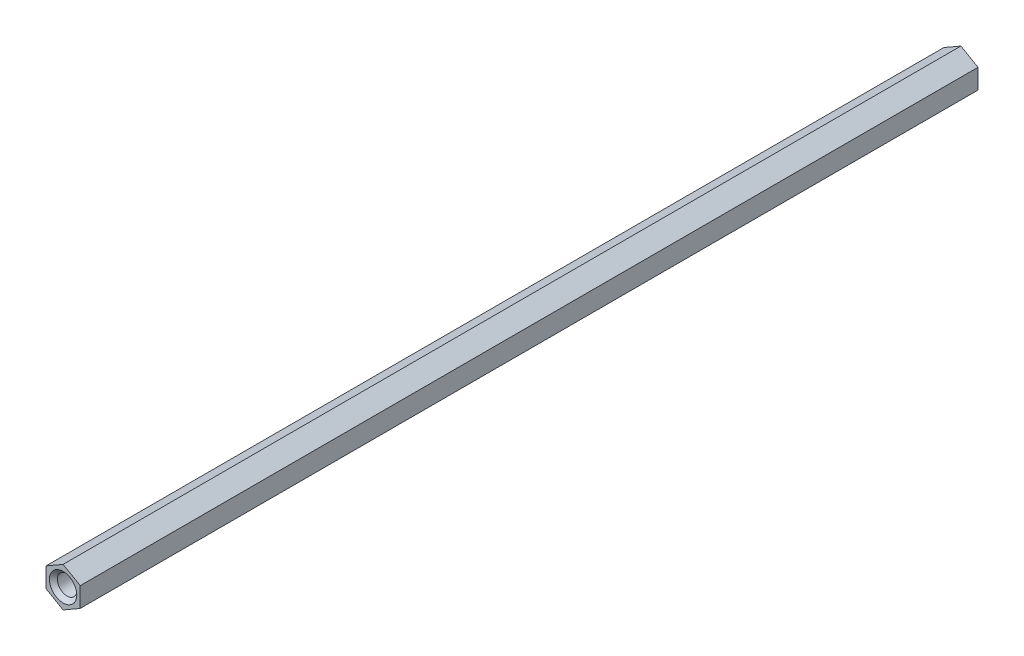
SolidWorks part; units mm, degrees
ref_plane "Front Plane" through (0, 0, 0) normal (0, 0, 1) x (1, 0, 0)
ref_plane "Top Plane" through (0, 0, 0) normal (0, 1, 0) x (1, 0, 0)
ref_plane "Right Plane" through (0, 0, 0) normal (1, 0, 0) x (0, 0, -1)
sketch "Sketch1" plane through (0, 0, 0) normal (0, 0, 1) x (1, 0, 0)
  line L0 (-4.7625, 0) -> (4.7625, 0) construction
  line L9 (0, 5.4993) -> (-4.7625, 2.7496) construction
  line L10 (-4.7625, 2.7496) -> (-4.7625, -2.7496) construction
  line L11 (-4.7625, -2.7496) -> (0, -5.4993) construction
  line L12 (0, -5.4993) -> (4.7625, -2.7496) construction
  line L13 (4.7625, -2.7496) -> (4.7625, 2.7496) construction
  line L14 (4.7625, 2.7496) -> (0, 5.4993) construction
  circle A3 centre (0, 0) radius 4.7625 construction
  point P4 (0, 0)
  dimension "Width" = 9.525
sketch "Sketch2" plane through (0, 0, 0) normal (1, 0, 0) x (0, 0, -1)
  line L0 (125, 5.4993) -> (-125, 5.4993) construction
  point P3 (-114.0463, 5.4993)
  point P4 (0, 5.4993)
  point P5 (114.0463, 5.4993)
  dimension "Length" = 250
  dimension "D1" = 10.9537
  dimension "D2" = 10.9537
sketch "Sketch3" plane through (0, 0, 0) normal (0, 0, 1) x (1, 0, 0)
  line L1 (0, 5.4993) -> (4.7625, 2.7496)
  line L2 (4.7625, 2.7496) -> (4.7625, -2.7496)
  line L3 (4.7625, -2.7496) -> (0, -5.4993)
  line L4 (0, -5.4993) -> (-4.7625, -2.7496)
  line L5 (-4.7625, -2.7496) -> (-4.7625, 2.7496)
  line L6 (-4.7625, 2.7496) -> (0, 5.4993)
extrude "Boss-Extrude1" add sketch "Sketch3" along normal mid plane 250
sketch "Sketch6" plane through (0, 0, 125) normal (0, 0, 1) x (1, 0, 0)
  point P0 (0, 0)
hole_wizard "1/4-28 Tapped Hole1" positions "Sketch6" profile "Sketch5" tap size "1/4-28" standard "ANSI Inch"
sketch "Sketch5" plane through (0, 0, 125) normal (1, 0, 0) x (0, -1, 0)
  line L0 (0, 0) -> (0, 16.8654)
  line L1 (0, 16.8654) -> (2.7051, 15.24)
  line L2 (2.7051, 15.24) -> (2.7051, 1.1049)
  line L3 (2.7051, 1.1049) -> (3.81, 0)
  line L5 (3.81, 0) -> (0, 0)
  line L6 (-2.7051, 1.1049) -> (-3.81, 0) construction
  line L10 (0, 16.8654) -> (-2.7051, 15.24) construction
  line L11 (0, -6.35) -> (0, 107.95) construction
  dimension "Tap Drill Dia." = 5.4102
  dimension "Tap Drill Depth" = 15.24
  dimension "Near C'Sink Dia." = 7.62
  dimension "Near C'Sink Angle" = 90
  dimension "Drill Angle" = 118
cosmetic thread "Hole Thread1" parameters "D1"=12.7, "D2"=6.35
sketch "Sketch9" plane through (0, 0, -125) normal (0, 0, -1) x (-1, 0, 0)
  point P0 (0, 0)
hole_wizard "1/4-28 Tapped Hole2" positions "Sketch9" profile "Sketch8" tap size "1/4-28" standard "ANSI Inch"
cosmetic thread "Hole Thread2" parameters "D1"=12.7, "D2"=6.35
sketch "Sketch8" plane through (0, 0, -125) normal (1, 0, 0) x (0, 1, 0)
  line L0 (0, 0) -> (0, 18.8593)
  line L1 (0, 18.8593) -> (2.7051, 17.2339)
  line L2 (2.7051, 17.2339) -> (2.7051, 1.1049)
  line L3 (2.7051, 1.1049) -> (3.81, 0)
  line L5 (3.81, 0) -> (0, 0)
  line L6 (-2.7051, 1.1049) -> (-3.81, 0) construction
  line L10 (0, 18.8593) -> (-2.7051, 17.2339) construction
  line L11 (0, -6.35) -> (0, 107.95) construction
  dimension "Tap Drill Dia." = 5.4102
  dimension "Tap Drill Depth" = 17.2339
  dimension "Near C'Sink Dia." = 7.62
  dimension "Near C'Sink Angle" = 90
  dimension "Drill Angle" = 118
equation "\"D1@Boss-Extrude1\" = \"Length@Sketch2\""
equation "\"D1@Sketch2\" = \"Width@Sketch1\" * 1.15"
equation "\"D2@Sketch2\"=\"D1@Sketch2\""
